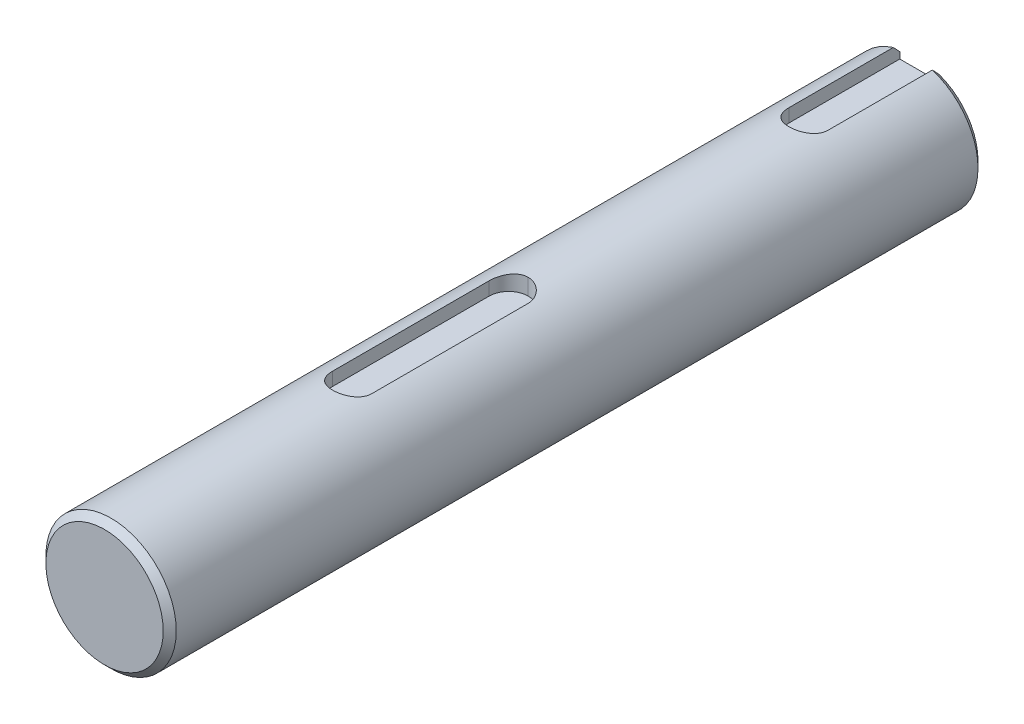
SolidWorks part; units mm, degrees
ref_plane "前视基准面" through (0, 0, 0) normal (0, 0, 1) x (1, 0, 0)
ref_plane "上视基准面" through (0, 0, 0) normal (0, 1, 0) x (1, 0, 0)
ref_plane "右视基准面" through (0, 0, 0) normal (1, 0, 0) x (0, 0, -1)
sketch "草图1" plane through (0, 0, 0) normal (0, 0, 1) x (1, 0, 0)
  line L0 (-87.1056, 0) -> (87.1056, 0) construction
  line L1 (0, 87.1056) -> (0, -87.1056) construction
  circle A0 centre (0, 0) radius 20
  dimension "D1" = 40
extrude "凸台-拉伸1" add sketch "草图1" along normal blind 100 and the other way blind 150
sketch "草图4" plane through (0, 0, 0) normal (0, 0, 1) x (1, 0, 0)
  line L0 (0, 0) -> (0, 114.7407) construction
  line L1 (-6, 39.304) -> (6, 39.304)
  line L2 (-6, 39.304) -> (-6, 15)
  line L3 (-6, 15) -> (6, 15)
  line L4 (6, 39.304) -> (6, 15)
  circle A0 centre (0, 0) radius 20 construction
  dimension "D1" = 12
  dimension "D2" = 15
extrude "切除-拉伸2" cut sketch "草图4" against normal mid plane 60
fillet "圆角1" radius 6 4 edges at (6, 17.0394, -30) (-6, 17.0394, -30) (6, 17.0394, 30) (-6, 17.0394, 30)
sketch "草图5" plane through (0, 0, -150) normal (0, 0, -1) x (-1, 0, 0)
  line L0 (0, 0) -> (0, 128.1777) construction
  line L1 (-6, 38.4892) -> (6, 38.4892)
  line L2 (-6, 38.4892) -> (-6, 15)
  line L3 (-6, 15) -> (6, 15)
  line L4 (6, 38.4892) -> (6, 15)
  circle A1 centre (0, 0) radius 20 construction
  dimension "D1" = 12
  dimension "D2" = 15
extrude "切除-拉伸3" cut sketch "草图5" against normal blind 40
fillet "圆角2" radius 6 2 edges at (6, 17.0394, -110) (-6, 17.0394, -110)
chamfer "倒角1" distance 2 angle 45 2 edges at (0, -20, -150) (20, 0, 100)
